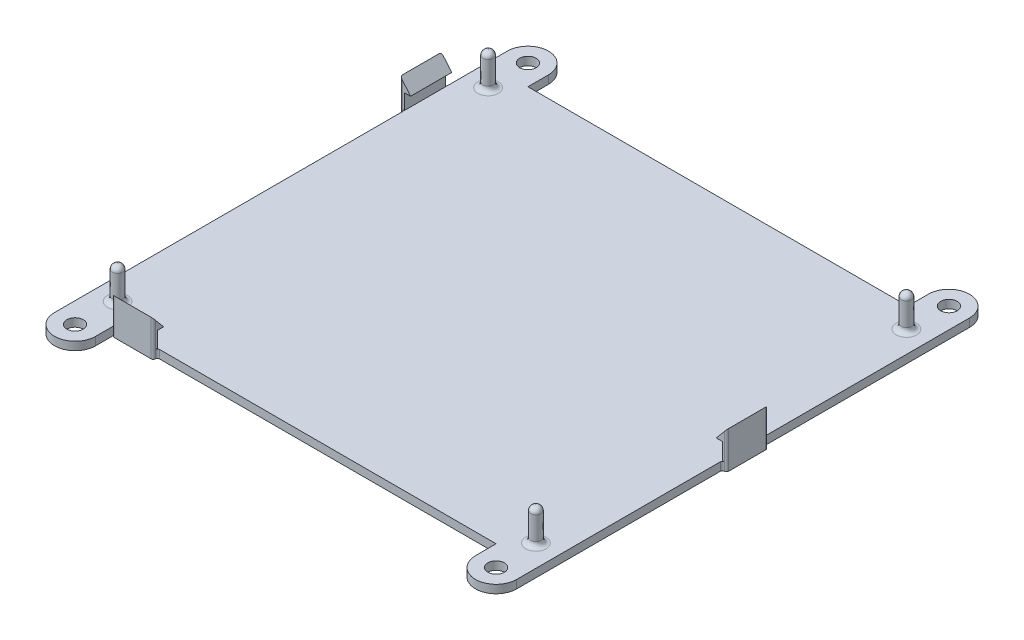
SolidWorks part; units mm, degrees
ref_plane "Front Plane" through (0, 0, 0) normal (0, 0, 1) x (1, 0, 0)
ref_plane "Top Plane" through (0, 0, 0) normal (0, 1, 0) x (1, 0, 0)
ref_plane "Right Plane" through (0, 0, 0) normal (1, 0, 0) x (0, 0, -1)
sketch "Sketch2" plane through (0, 0, 0) normal (0, 1, 0) x (1, 0, 0)
  line L1 (-56.134, -50) -> (56.134, -50)
  line L2 (-56.134, -50) -> (-56.134, 50)
  line L3 (-56.134, 50) -> (56.134, 50)
  line L4 (56.134, -50) -> (56.134, 50)
  line L5 (-56.134, -50) -> (56.134, 50) construction
  line L6 (-56.134, 50) -> (56.134, -50) construction
  line L11 (-44.9072, -40) -> (44.9072, 40) construction
  line L12 (-44.9072, 40) -> (44.9072, -40) construction
  point P0 (0, 0)
  point P6 (0, 0)
  dimension "D1" = 100
  dimension "D2" = 112.268
extrude "Boss-Extrude2" add sketch "Sketch2" along normal blind 2
sketch "Sketch1" plane through (0, 0, 0) normal (0, 1, 0) x (1, 0, 0)
  line L0 (-50.8, -45) -> (50.8, -45) construction
  line L1 (-50.8, -45) -> (-50.8, 45) construction
  line L2 (-50.8, 45) -> (50.8, 45) construction
  line L3 (50.8, -45) -> (50.8, 45) construction
  line L4 (-50.8, -45) -> (50.8, 45) construction
  line L5 (-50.8, 45) -> (50.8, -45) construction
  circle A0 centre (-50.8, 45) radius 1.275
  circle A1 centre (50.8, 45) radius 1.275
  circle A2 centre (50.8, -45) radius 1.275
  circle A3 centre (-50.8, -45) radius 1.275
  point P0 (0, 0)
  dimension "D3" = 2.55
  dimension "D1" = 101.6
  dimension "D2" = 90
extrude "Boss-Extrude1" add sketch "Sketch1" along normal blind 10
sketch "Sketch3" plane through (0, 0, 0) normal (0, 0, 1) x (1, 0, 0)
  line L0 (57.134, 9) -> (54.634, 6)
  line L1 (56.134, 0) -> (57.134, 0)
  line L2 (56.134, 0) -> (56.134, 6)
  line L4 (57.134, 0) -> (57.134, 9)
  line L5 (54.634, 6) -> (56.134, 6)
  line L6 (-56.134, 2) -> (56.134, 2) construction
  dimension "D1" = 4
  dimension "D2" = 1
  dimension "D3" = 1.5
  dimension "D4" = 3
extrude "Boss-Extrude3" add sketch "Sketch3" along normal mid plane 10
ref_plane "Plane1" through (-41.134, 0, 0) normal (-1, 0, 0) x (0, 0, 1)
sketch "Sketch4" plane through (-41.134, 0, 0) normal (-1, 0, 0) x (0, 0, 1)
  line L0 (51, 8.75) -> (48.5, 5.75)
  line L1 (50, 0) -> (51, 0)
  line L2 (50, 0) -> (50, 5.75)
  line L3 (51, 0) -> (51, 8.75)
  line L4 (48.5, 5.75) -> (50, 5.75)
  line L10 (50, 2) -> (50, 0) construction
  line L11 (-50, 0) -> (50, 0) construction
  line L12 (-50, 2) -> (50, 2) construction
  dimension "D1" = 1
  dimension "D2" = 3
  dimension "D3" = 3.75
  dimension "D4" = 1.5
extrude "Boss-Extrude4" add sketch "Sketch4" along normal mid plane 10
ref_plane "Plane2" through (0, 0, -35) normal (0, 0, -1) x (-1, 0, 0)
sketch "Sketch5" plane through (0, 0, -35) normal (0, 0, -1) x (-1, 0, 0)
  line L0 (57.134, 8.75) -> (54.634, 5.75)
  line L1 (56.134, 0) -> (57.134, 0)
  line L2 (56.134, 0) -> (56.134, 5.75)
  line L3 (57.134, 0) -> (57.134, 8.75)
  line L4 (54.634, 5.75) -> (56.134, 5.75)
  line L6 (56.134, 0) -> (46.134, 0) construction
  line L7 (56.134, 2) -> (56.134, 0) construction
  line L8 (56.134, 2) -> (46.134, 2) construction
  dimension "D1" = 1
  dimension "D2" = 3
  dimension "D3" = 1.5
  dimension "D4" = 3.75
extrude "Boss-Extrude5" add sketch "Sketch5" along normal mid plane 10
fillet "Fillet1" radius 1.2 8 edges at (-50.8, 10, -43.725) (-50.8, 10, 46.275) (50.8, 10, 46.275) (50.8, 10, -43.725) (50.8, 2, 43.725) (-50.8, 2, 43.725) (50.8, 2, -46.275) (-50.8, 2, -46.275)
fillet "Fillet2" radius 0.5 12 edges at (-56.134, 1, -30) (-56.134, 1, -40) (56.134, 1, 5) (56.134, 1, -5) (-46.134, 1, 50) (-36.134, 1, 50) (-57.134, 4.375, -30) (-57.134, 4.375, -40) (57.134, 4.5, -5) (57.134, 4.5, 5) (-36.134, 4.375, 51) (-46.134, 4.375, 51)
sketch "Sketch6" plane through (0, 0, 0) normal (0, 1, 0) x (1, 0, 0)
  line L0 (-5.5, 0) -> (5.5, 0) construction
  line L1 (56.134, -50) -> (46.134, -50)
  line L2 (56.134, -50) -> (56.134, -55)
  line L3 (56.134, -55) -> (46.134, -55) construction
  line L4 (46.134, -50) -> (46.134, -55)
  line L5 (56.134, 55) -> (46.134, 55) construction
  line L6 (46.134, 50) -> (46.134, 55)
  line L7 (56.134, 50) -> (56.134, 55)
  line L8 (56.134, 50) -> (46.134, 50)
  line L9 (0, -5.5) -> (0, 5.5) construction
  line L10 (-56.134, 55) -> (-46.134, 55) construction
  line L11 (-56.134, -55) -> (-46.134, -55) construction
  line L12 (-56.134, 50) -> (-46.134, 50)
  line L13 (-56.134, 50) -> (-56.134, 55)
  line L14 (-46.134, 50) -> (-46.134, 55)
  line L15 (-46.134, -50) -> (-46.134, -55)
  line L16 (-56.134, -50) -> (-56.134, -55)
  line L17 (-56.134, -50) -> (-46.134, -50)
  arc A0 (46.134, -55) -> (56.134, -55) centre (51.134, -55) ccw
  circle A1 centre (51.134, -55) radius 2
  circle A2 centre (51.134, 55) radius 2
  arc A3 (46.134, 55) -> (56.134, 55) centre (51.134, 55) cw
  arc A4 (-46.134, 55) -> (-56.134, 55) centre (-51.134, 55) ccw
  circle A5 centre (-51.134, 55) radius 2
  circle A6 centre (-51.134, -55) radius 2
  arc A7 (-46.134, -55) -> (-56.134, -55) centre (-51.134, -55) cw
  dimension "D3" = 4
  dimension "D1" = 10
  dimension "D2" = 5
extrude "Boss-Extrude6" add sketch "Sketch6" along normal up to surface (2 mm away) up to face at (50.8, 2, 42.525)
